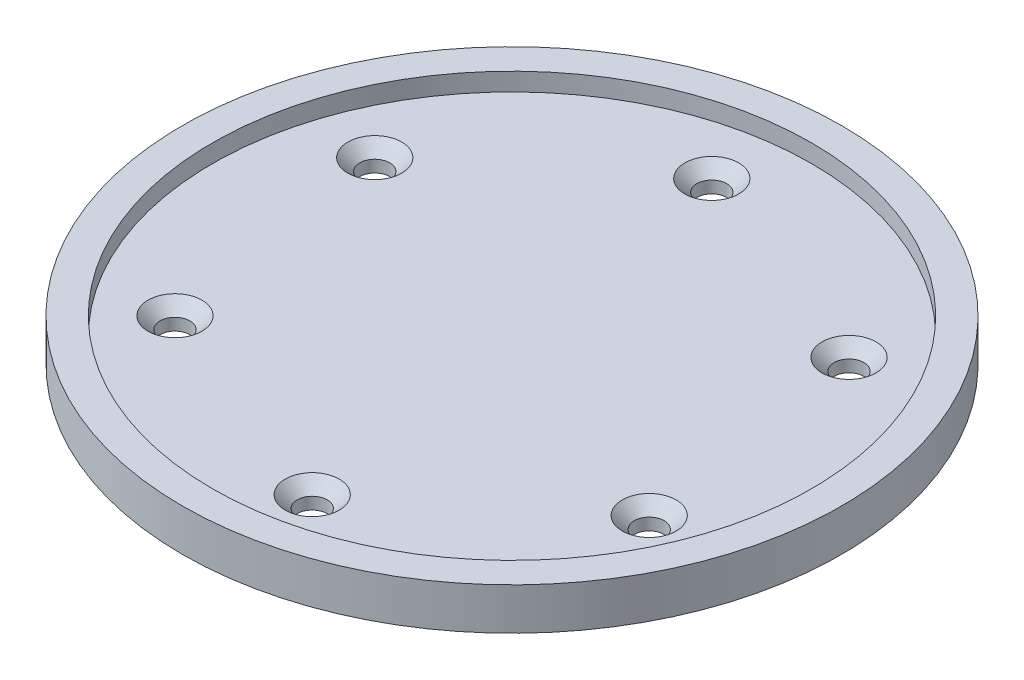
SolidWorks part; units mm, degrees
material "PBT General Purpose"
ref_plane "Front Plane" through (0, 0, 0) normal (0, 0, 1) x (1, 0, 0)
ref_plane "Top Plane" through (0, 0, 0) normal (0, 1, 0) x (1, 0, 0)
ref_plane "Right Plane" through (0, 0, 0) normal (1, 0, 0) x (0, 0, -1)
sketch "Sketch1" plane through (0, 0, 0) normal (0, 0, 1) x (1, 0, 0)
  line L0 (0, 0) -> (0, 21.4941) construction
  line L1 (50, 3.4786) -> (50, 6.4786)
  line L2 (50, 6.4786) -> (55, 6.4786)
  line L9 (50, 3.4786) -> (0, 3.4786)
  line L10 (0, -0.5214) -> (0, 3.4786)
  line L11 (0, -0.5214) -> (55, -0.5214)
  line L12 (55, -0.5214) -> (55, 6.4786)
  dimension "D2" = 50
  dimension "D5" = 5
  dimension "D3" = 4
  dimension "D7" = 3
revolve "Revolve1" add sketch "Sketch1" angle 360 about L0
sketch "Sketch2" plane through (0, 3.4786, 0) normal (0, 1, 0) x (1, 0, 0)
  circle A0 centre (-6.1774, 39.5201) radius 2.5
  circle A1 centre (-37.3141, 14.4103) radius 2.5
  circle A2 centre (-31.1367, -25.1098) radius 2.5
  circle A3 centre (6.1774, -39.5201) radius 2.5
  circle A4 centre (37.3141, -14.4103) radius 2.5
  circle A5 centre (31.1367, 25.1098) radius 2.5
  dimension "D1" = 5
extrude "Cut-Extrude1" cut sketch "Sketch2" against normal through all
chamfer "Chamfer1" distance 2 angle 45 6 edges at (31.1367, 3.4786, -22.6098) (37.3141, 3.4786, 16.9103) (-31.1367, 3.4786, 27.6098) (-37.3141, 3.4786, -11.9103) (-6.1774, 3.4786, -37.0201) (6.1774, 3.4786, 42.0201)
